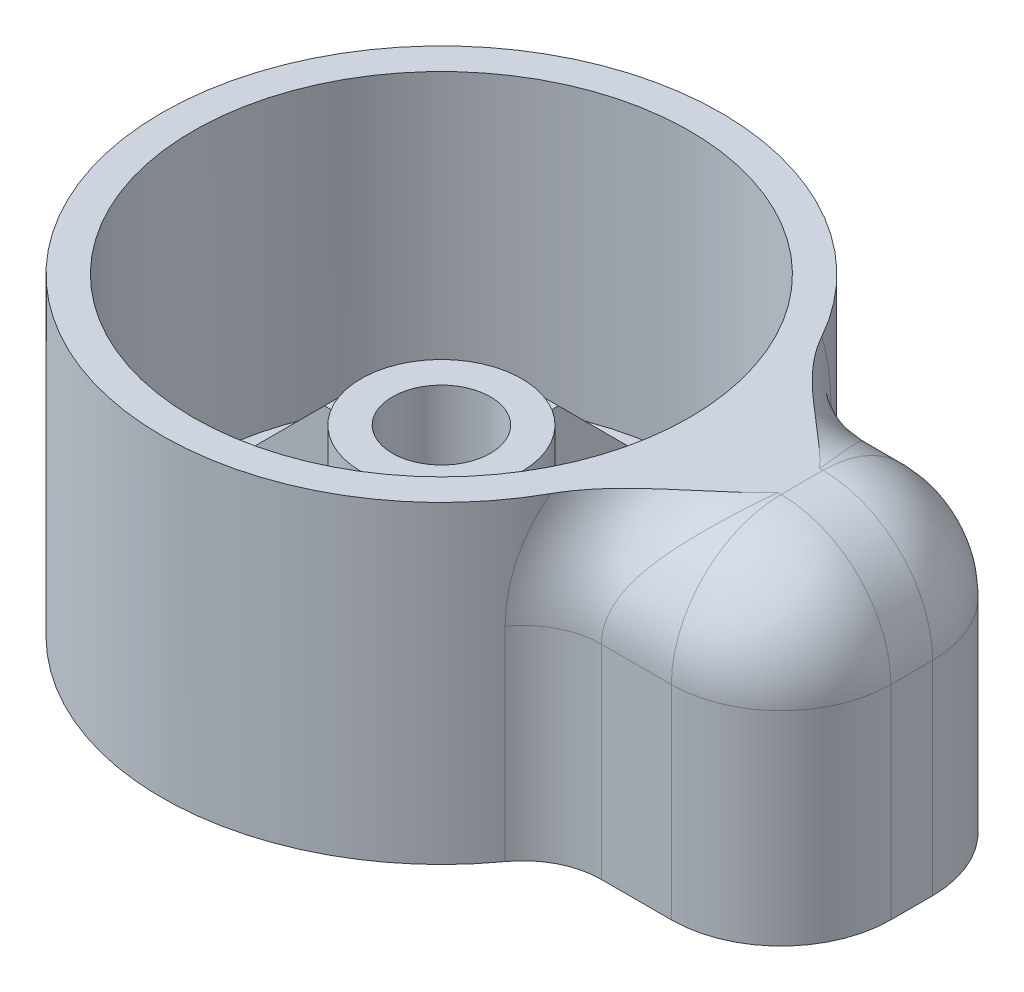
SolidWorks part; units mm, degrees
ref_plane "Front Plane" through (0, 0, 0) normal (0, 0, 1) x (1, 0, 0)
ref_plane "Top Plane" through (0, 0, 0) normal (0, 1, 0) x (1, 0, 0)
ref_plane "Right Plane" through (0, 0, 0) normal (1, 0, 0) x (0, 0, -1)
sketch "Sketch1" plane through (0, 0, 0) normal (0, 1, 0) x (1, 0, 0)
  circle A0 centre (0, 0) radius 1.875
  circle A1 centre (0, 0) radius 20
  dimension "D1" = 3.75
  dimension "D2" = 40
extrude "Boss-Extrude1" add sketch "Sketch1" along normal blind 1
sketch "Sketch2" plane through (0, 1, 0) normal (0, 1, 0) x (1, 0, 0)
  line L0 (4.2, -1.25) -> (4.2, 1.25) construction
  line L1 (3.2, -1.25) -> (3.2, 1.25)
  line L2 (5.2, -1.25) -> (5.2, 1.25)
  line L3 (13, -2) -> (13, 2) construction
  line L4 (12, -2) -> (12, 2)
  line L5 (14, -2) -> (14, 2)
  line L6 (0, 0) -> (18.7895, 0) construction
  arc A0 (3.2, -1.25) -> (5.2, -1.25) centre (4.2, -1.25) ccw
  arc A1 (5.2, 1.25) -> (3.2, 1.25) centre (4.2, 1.25) ccw
  arc A2 (12, -2) -> (14, -2) centre (13, -2) ccw
  arc A3 (14, 2) -> (12, 2) centre (13, 2) ccw
  point P2 (4.2, 0)
  point P7 (13, 0)
  dimension "D1" = 1
  dimension "D2" = 1
  dimension "D3" = 4.2
  dimension "D4" = 13
  dimension "D5" = 2.5
  dimension "D6" = 4
extrude "Cut-Extrude1" cut sketch "Sketch2" against normal through all
sketch "Sketch3" plane through (0, 1, 0) normal (0, 1, 0) x (1, 0, 0)
  circle A0 centre (0, 0) radius 1.875
  circle A1 centre (0, 0) radius 2.675
  circle A2 centre (0, 0) radius 1.875 construction
  dimension "D1" = 0.8
extrude "Boss-Extrude2" add sketch "Sketch3" along normal blind 3
sketch "Sketch4" plane through (0, 0, 0) normal (0, -1, 0) x (1, 0, 0)
  circle A0 centre (0, 0) radius 20
  circle A1 centre (0, 0) radius 20 construction
  circle A2 centre (0, 0) radius 18.8
  dimension "D1" = 1.2
extrude "Boss-Extrude3" [suppressed] add sketch "Sketch4" along normal blind 6
sketch "Sketch5" plane through (0, 1, 0) normal (0, 1, 0) x (1, 0, 0)
  line L1 (6, 5) -> (18, 5)
  line L2 (6, 5) -> (6, -5)
  line L3 (6, -5) -> (18, -5)
  line L4 (18, 5) -> (18, -5)
  point P4 (6, 0)
  dimension "D1" = 6
  dimension "D2" = 12
  dimension "D3" = 10
extrude "Boss-Extrude4" add sketch "Sketch5" along normal blind 11
sketch "Sketch6" plane through (6, 0, 0) normal (-1, 0, 0) x (0, 0, 1)
  line L0 (-5, 1) -> (5, 1) construction
  line L1 (-3.8, 1) -> (3.8, 1)
  line L2 (-3.8, 1) -> (-3.8, 10.8)
  line L3 (-3.8, 10.8) -> (3.8, 10.8)
  line L4 (3.8, 1) -> (3.8, 10.8)
  line L5 (-5, 12) -> (5, 12) construction
  line L6 (-5, 12) -> (-5, 1) construction
  line L7 (5, 12) -> (5, 1) construction
  dimension "D1" = 1.2
  dimension "D2" = 1.2
  dimension "D3" = 1.2
extrude "Cut-Extrude2" cut sketch "Sketch6" against normal offset from surface (10.8 mm away) 1.2 up to face at (18, 6.5, 0)
fillet "Fillet2" radius 3 5 edges at (11.4, 10.8, 3.8) (16.8, 5.9, 3.8) (16.8, 5.9, -3.8) (11.4, 10.8, -3.8) (16.8, 10.8, 0)
fillet "Fillet3" radius 4.2 5 edges at (18, 6.5, 5) (18, 6.5, -5) (12, 12, -5) (18, 12, 0) (12, 12, 5)
sketch "Sketch7" plane through (0, 1, 0) normal (0, 1, 0) x (1, 0, 0)
  circle A0 centre (0, 0) radius 9.5
  dimension "D1" = 19
extrude "Cut-Extrude3" cut sketch "Sketch7" along normal through all
sketch "Sketch8" plane through (0, 1, 0) normal (0, 1, 0) x (1, 0, 0)
  circle A0 centre (0, 0) radius 1.875
  circle A1 centre (0, 0) radius 3.075
  dimension "D1" = 3.75
  dimension "D2" = 1.2
extrude "Boss-Extrude5" add sketch "Sketch8" along normal blind 6
sketch "Sketch9" plane through (0, 1, 0) normal (0, 1, 0) x (1, 0, 0)
  line L0 (0, 1.875) -> (0, 6.875)
  line L1 (0, -1.875) -> (0, -6.875)
  line L2 (-1.875, 0) -> (-6.875, 0)
  circle A0 centre (0, 0) radius 1.875 construction
  dimension "D1" = 5
extrude "Extrude-Thin1" add sketch "Sketch9" along normal blind 5 thin thin type mid plane wall 1.2
chamfer "Chamfer1" distance 3 angle 45 3 edges at (0, 6, 6.875) (0, 6, -6.875) (-6.875, 6, 0)
sketch "Sketch11" plane through (0, 12, 0) normal (0, 1, 0) x (1, 0, 0)
  circle A0 centre (0, 0) radius 9.5
  circle A1 centre (0, 0) radius 10.7
  dimension "D1" = 1.2
extrude "Boss-Extrude7" add sketch "Sketch11" against normal up to body
sketch "Sketch12" plane through (0, 1, 0) normal (0, 1, 0) x (1, 0, 0)
  line L0 (4.2, 2.25) -> (3.1174, 2.25)
  line L1 (4.2, -2.25) -> (3.1174, -2.25)
  line L2 (4.2, 2.25) -> (4.2, -2.25)
  arc A0 (5.2, 1.25) -> (3.2, 1.25) centre (4.2, 1.25) ccw construction
  arc A1 (0.6, -3.0159) -> (0.6, 3.0159) centre (0, 0) ccw construction
  arc A2 (3.2, -1.25) -> (5.2, -1.25) centre (4.2, -1.25) ccw construction
  circle A3 centre (0, 0) radius 3.075 construction
  arc A4 (2.6814, 1.5052) -> (2.6814, -1.5052) centre (0, 0) cw
  arc A5 (3.1174, -2.25) -> (2.6814, -1.5052) centre (3.1174, -1.75) cw
  arc A6 (2.6814, 1.5052) -> (3.1174, 2.25) centre (3.1174, 1.75) cw
  point P18 (2.096, -2.25)
  point P21 (2.096, 2.25)
  dimension "D1" = 0.5
extrude "Cut-Extrude4" cut sketch "Sketch12" against normal through all
fillet "Fillet4" radius 1 5 edges at (8.7069, 4.4, 3.8) (9.126, 10.1699, 2.6394) (9.5, 10.8, 0) (8.9396, 9.5803, -3.2147) (8.7069, 4.4, -3.8)
sketch "Sketch13" plane through (0, 1, 0) normal (0, 1, 0) x (1, 0, 0)
  line L3 (13.8, 5) -> (9.4599, 5)
  line L4 (18, -0.8) -> (18, 0.8)
  line L5 (9.4599, -5) -> (13.8, -5)
  line L6 (13.8, 5) -> (9.4599, 5)
  line L7 (18, -0.8) -> (18, 0.8)
  line L8 (9.4599, -5) -> (13.8, -5)
  circle A1 centre (0, 0) radius 20
  circle A2 centre (0, 0) radius 20
  arc A5 (9.4599, 5) -> (9.4599, -5) centre (0, 0) ccw
  arc A6 (18, 0.8) -> (13.8, 5) centre (13.8, 0.8) ccw
  arc A7 (13.8, -5) -> (18, -0.8) centre (13.8, -0.8) ccw
  arc A8 (9.4599, 5) -> (9.4599, -5) centre (0, 0) ccw
  arc A9 (18, 0.8) -> (13.8, 5) centre (13.8, 0.8) ccw
  arc A10 (13.8, -5) -> (18, -0.8) centre (13.8, -0.8) ccw
  dimension "D1" = 0
  dimension "D2" = 0
extrude "Cut-Extrude5" cut sketch "Sketch13" against normal blind 10
fillet "Fillet5" radius 3 4 edges at (9.8348, 10.2448, -4.2151) (10.1667, 11.148, 3.336) (9.4599, 3.9, -5) (9.4599, 3.9, 5)
